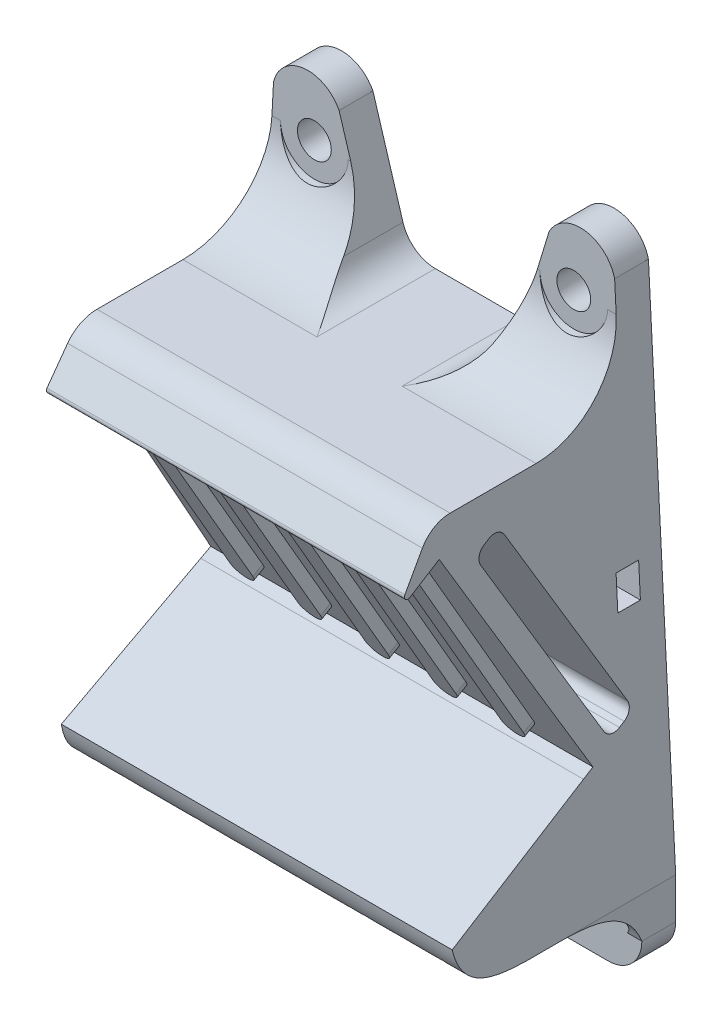
SolidWorks part; units mm, degrees
ref_plane "Alzado" through (0, 0, 0) normal (0, 0, 1) x (1, 0, 0)
ref_plane "Planta" through (0, 0, 0) normal (0, 1, 0) x (1, 0, 0)
ref_plane "Vista lateral" through (0, 0, 0) normal (1, 0, 0) x (0, 0, -1)
sketch "Croquis1" plane through (0, 0, 0) normal (0, 0, 1) x (1, 0, 0)
  line L0 (0, 0) -> (27.8544, 27.8544) construction
  line L1 (0, 0) -> (-42.4264, 42.4264) construction
  line L2 (0, 0) -> (0, 42.4264) construction
  line L3 (15.25, -15.25) -> (-15.25, -15.25) construction
  line L4 (15.25, -15.25) -> (15.25, 15.25) construction
  line L5 (15.25, 15.25) -> (-15.25, 15.25) construction
  line L6 (-15.25, -15.25) -> (-15.25, 15.25) construction
  line L7 (15.25, -15.25) -> (-15.25, 15.25) construction
  line L8 (15.25, 15.25) -> (-15.25, -15.25) construction
  line L9 (0, 42.4264) -> (-20, 42.4264) construction
  line L10 (-42.4264, 42.4264) -> (-38.8909, 45.9619) construction
  line L11 (-38.8909, 45.9619) -> (-31.0962, 38.1673) construction
  line L13 (-42.4264, 42.4264) -> (-45.9619, 38.8909) construction
  line L14 (-45.9619, 38.8909) -> (-38.1673, 31.0962) construction
  line L16 (38.8909, 45.9619) -> (31.0962, 38.1673) construction
  line L17 (42.4264, 42.4264) -> (38.8909, 45.9619) construction
  line L18 (42.4264, 42.4264) -> (45.9619, 38.8909) construction
  line L19 (-45.9619, -38.8909) -> (-38.1673, -31.0962) construction
  line L20 (0, 0) -> (-15.25, 0) construction
  line L21 (45.9619, 38.8909) -> (38.1673, 31.0962) construction
  line L22 (42.4264, -42.4264) -> (45.9619, -38.8909) construction
  line L23 (42.4264, -42.4264) -> (38.8909, -45.9619) construction
  line L24 (38.8909, -45.9619) -> (31.0962, -38.1673) construction
  line L27 (-38.8909, -45.9619) -> (-31.0962, -38.1673) construction
  line L28 (-42.4264, -42.4264) -> (-38.8909, -45.9619) construction
  line L29 (-42.4264, -42.4264) -> (-45.9619, -38.8909) construction
  line L30 (45.9619, -38.8909) -> (38.1673, -31.0962) construction
  line L31 (-15, 80) -> (15, 80) construction
  line L32 (0, -15.25) -> (0, -80) construction
  line L36 (-15, -80) -> (15, -80) construction
  line L41 (-12.268, -54) -> (-12.268, -67.5) construction
  line L43 (-10.268, -54) -> (-10.268, -67.5) construction
  line L105 (0, -80) -> (0, -83) construction
  line L106 (-15, -80) -> (0, -83) construction
  line L127 (15, -80) -> (0, -83) construction
  line L131 (0, 80) -> (0, 83) construction
  line L132 (-15, 80) -> (15, 80) construction
  line L136 (15, 80) -> (0, 83) construction
  line L157 (-15, 80) -> (0, 83) construction
  line L160 (-14, 30) -> (-17.8891, 33.8891) construction
  line L161 (-31.0962, 38.1673) -> (-22.6531, 29.7242) construction
  line L162 (-17.5359, 31.6883) -> (-15, 80) construction
  line L163 (17.5359, 31.6883) -> (15, 80) construction
  line L164 (31.0962, 38.1673) -> (22.6531, 29.7242) construction
  line L165 (31.0962, -38.1673) -> (22.6531, -29.7242) construction
  line L166 (17.5359, -31.6883) -> (15, -80) construction
  line L167 (-17.5359, -31.6883) -> (-15, -80) construction
  line L168 (-31.0962, -38.1673) -> (-22.6531, -29.7242) construction
  line L169 (-8.268, -54) -> (-8.268, -67.5) construction
  line L170 (-6.268, -54) -> (-6.268, -67.5) construction
  line L171 (-4.268, -54) -> (-4.268, -67.5) construction
  line L172 (-2.268, -54) -> (-2.268, -67.5) construction
  line L173 (-8.268, -35) -> (-8.268, -48.5) construction
  line L174 (-6.268, -35) -> (-6.268, -48.5) construction
  line L175 (-4.268, -35) -> (-4.268, -48.5) construction
  line L176 (-2.268, -35) -> (-2.268, -48.5) construction
  line L177 (-12.268, -35) -> (-12.268, -48.5) construction
  line L178 (-10.268, -35) -> (-10.268, -48.5) construction
  line L179 (10.268, -35) -> (10.268, -48.5) construction
  line L180 (12.268, -35) -> (12.268, -48.5) construction
  line L181 (2.268, -35) -> (2.268, -48.5) construction
  line L182 (4.268, -35) -> (4.268, -48.5) construction
  line L183 (6.268, -35) -> (6.268, -48.5) construction
  line L184 (8.268, -35) -> (8.268, -48.5) construction
  line L185 (2.268, -54) -> (2.268, -67.5) construction
  line L186 (4.268, -54) -> (4.268, -67.5) construction
  line L187 (6.268, -54) -> (6.268, -67.5) construction
  line L188 (8.268, -54) -> (8.268, -67.5) construction
  line L189 (10.268, -54) -> (10.268, -67.5) construction
  line L190 (12.268, -54) -> (12.268, -67.5) construction
  line L191 (12.268, 54) -> (12.268, 67.5) construction
  line L192 (10.268, 54) -> (10.268, 67.5) construction
  line L193 (8.268, 54) -> (8.268, 67.5) construction
  line L194 (6.268, 54) -> (6.268, 67.5) construction
  line L195 (4.268, 54) -> (4.268, 67.5) construction
  line L196 (2.268, 54) -> (2.268, 67.5) construction
  line L197 (8.268, 35) -> (8.268, 48.5) construction
  line L198 (6.268, 35) -> (6.268, 48.5) construction
  line L199 (4.268, 35) -> (4.268, 48.5) construction
  line L200 (2.268, 35) -> (2.268, 48.5) construction
  line L201 (12.268, 35) -> (12.268, 48.5) construction
  line L202 (10.268, 35) -> (10.268, 48.5) construction
  line L203 (-10.268, 35) -> (-10.268, 48.5) construction
  line L204 (-12.268, 35) -> (-12.268, 48.5) construction
  line L205 (-2.268, 35) -> (-2.268, 48.5) construction
  line L206 (-4.268, 35) -> (-4.268, 48.5) construction
  line L207 (-6.268, 35) -> (-6.268, 48.5) construction
  line L208 (-8.268, 35) -> (-8.268, 48.5) construction
  line L209 (-2.268, 54) -> (-2.268, 67.5) construction
  line L210 (-4.268, 54) -> (-4.268, 67.5) construction
  line L211 (-6.268, 54) -> (-6.268, 67.5) construction
  line L212 (-8.268, 54) -> (-8.268, 67.5) construction
  line L213 (-10.268, 54) -> (-10.268, 67.5) construction
  line L214 (-12.268, 54) -> (-12.268, 67.5) construction
  line L215 (-0.621, -15.7817) -> (-8.2129, -22.282) construction
  line L216 (-7.5625, -24.0416) -> (8.3607, -24.0416) construction
  line L217 (8.9758, -22.2532) -> (0.6445, -15.7529) construction
  line L218 (-7.5625, 24.0416) -> (8.3607, 24.0416) construction
  line L219 (8.9758, 22.2532) -> (0.6445, 15.7529) construction
  line L220 (-0.621, 15.7817) -> (-8.2129, 22.282) construction
  line L221 (-38.1673, 31.0962) -> (-28.2843, 21.2132) construction
  line L222 (-28.2843, -21.2132) -> (-38.1673, -31.0962) construction
  line L223 (28.2843, -21.2132) -> (38.1673, -31.0962) construction
  line L224 (38.1673, 31.0962) -> (28.2843, 21.2132) construction
  line L225 (-17.5359, 31.6883) -> (-15, 80)
  line L226 (-15, 80) -> (0, 83)
  line L227 (0, 83) -> (15, 80)
  line L228 (15, 80) -> (17.5359, 31.6883)
  line L229 (17.5359, 31.6883) -> (17.5359, -31.6883)
  line L230 (17.5359, -31.6883) -> (15, -80)
  line L231 (15, -80) -> (0, -83)
  line L232 (0, -83) -> (-15, -80)
  line L233 (-15, -80) -> (-17.5359, -31.6883)
  line L234 (-17.5359, -31.6883) -> (-17.5359, 31.6883)
  circle A0 centre (-15.25, 15.25) radius 4 construction
  circle A1 centre (-24.0416, 24.0416) radius 1.5 construction
  circle A2 centre (-38.8909, 38.8909) radius 1.5 construction
  circle A5 centre (38.8909, 38.8909) radius 1.5 construction
  circle A6 centre (24.0416, 24.0416) radius 1.5 construction
  circle A7 centre (15.25, 15.25) radius 4 construction
  circle A8 centre (15.25, -15.25) radius 4 construction
  circle A9 centre (24.0416, -24.0416) radius 1.5 construction
  circle A10 centre (38.8909, -38.8909) radius 1.5 construction
  circle A12 centre (-15.25, -15.25) radius 4 construction
  circle A13 centre (-24.0416, -24.0416) radius 1.5 construction
  circle A14 centre (-38.8909, -38.8909) radius 1.5 construction
  circle A18 centre (0, 0) radius 3.5 construction
  circle A19 centre (-11.5, -75) radius 1.5 construction
  circle A21 centre (-14, 30) radius 1.5 construction
  arc A27 (-12.268, -54) -> (-10.268, -54) centre (-11.268, -54) cw construction
  arc A28 (-12.268, -67.5) -> (-10.268, -67.5) centre (-11.268, -67.5) ccw construction
  circle A111 centre (11.5, -75) radius 1.5 construction
  circle A112 centre (11.5, 75) radius 1.5 construction
  circle A137 centre (-11.5, 75) radius 1.5 construction
  arc A138 (-22.6531, 29.7242) -> (-17.5359, 31.6883) centre (-20.5318, 31.8455) ccw construction
  arc A139 (22.6531, 29.7242) -> (17.5359, 31.6883) centre (20.5318, 31.8455) cw construction
  arc A140 (22.6531, -29.7242) -> (17.5359, -31.6883) centre (20.5318, -31.8455) ccw construction
  arc A141 (-22.6531, -29.7242) -> (-17.5359, -31.6883) centre (-20.5318, -31.8455) cw construction
  circle A142 centre (14, 30) radius 1.5 construction
  circle A143 centre (14, -30) radius 1.5 construction
  circle A144 centre (-14, -30) radius 1.5 construction
  arc A145 (-8.268, -67.5) -> (-6.268, -67.5) centre (-7.268, -67.5) ccw construction
  arc A146 (-8.268, -54) -> (-6.268, -54) centre (-7.268, -54) cw construction
  arc A147 (-4.268, -67.5) -> (-2.268, -67.5) centre (-3.268, -67.5) ccw construction
  arc A148 (-4.268, -54) -> (-2.268, -54) centre (-3.268, -54) cw construction
  arc A149 (-8.268, -48.5) -> (-6.268, -48.5) centre (-7.268, -48.5) ccw construction
  arc A150 (-8.268, -35) -> (-6.268, -35) centre (-7.268, -35) cw construction
  arc A151 (-4.268, -48.5) -> (-2.268, -48.5) centre (-3.268, -48.5) ccw construction
  arc A152 (-4.268, -35) -> (-2.268, -35) centre (-3.268, -35) cw construction
  arc A153 (-12.268, -48.5) -> (-10.268, -48.5) centre (-11.268, -48.5) ccw construction
  arc A154 (-12.268, -35) -> (-10.268, -35) centre (-11.268, -35) cw construction
  arc A155 (12.268, -35) -> (10.268, -35) centre (11.268, -35) ccw construction
  arc A156 (12.268, -48.5) -> (10.268, -48.5) centre (11.268, -48.5) cw construction
  arc A157 (4.268, -35) -> (2.268, -35) centre (3.268, -35) ccw construction
  arc A158 (4.268, -48.5) -> (2.268, -48.5) centre (3.268, -48.5) cw construction
  arc A159 (8.268, -35) -> (6.268, -35) centre (7.268, -35) ccw construction
  arc A160 (8.268, -48.5) -> (6.268, -48.5) centre (7.268, -48.5) cw construction
  arc A161 (4.268, -54) -> (2.268, -54) centre (3.268, -54) ccw construction
  arc A162 (4.268, -67.5) -> (2.268, -67.5) centre (3.268, -67.5) cw construction
  arc A163 (8.268, -54) -> (6.268, -54) centre (7.268, -54) ccw construction
  arc A164 (8.268, -67.5) -> (6.268, -67.5) centre (7.268, -67.5) cw construction
  arc A165 (12.268, -67.5) -> (10.268, -67.5) centre (11.268, -67.5) cw construction
  arc A166 (12.268, -54) -> (10.268, -54) centre (11.268, -54) ccw construction
  arc A167 (12.268, 54) -> (10.268, 54) centre (11.268, 54) cw construction
  arc A168 (12.268, 67.5) -> (10.268, 67.5) centre (11.268, 67.5) ccw construction
  arc A169 (8.268, 67.5) -> (6.268, 67.5) centre (7.268, 67.5) ccw construction
  arc A170 (8.268, 54) -> (6.268, 54) centre (7.268, 54) cw construction
  arc A171 (4.268, 67.5) -> (2.268, 67.5) centre (3.268, 67.5) ccw construction
  arc A172 (4.268, 54) -> (2.268, 54) centre (3.268, 54) cw construction
  arc A173 (8.268, 48.5) -> (6.268, 48.5) centre (7.268, 48.5) ccw construction
  arc A174 (8.268, 35) -> (6.268, 35) centre (7.268, 35) cw construction
  arc A175 (4.268, 48.5) -> (2.268, 48.5) centre (3.268, 48.5) ccw construction
  arc A176 (4.268, 35) -> (2.268, 35) centre (3.268, 35) cw construction
  arc A177 (12.268, 48.5) -> (10.268, 48.5) centre (11.268, 48.5) ccw construction
  arc A178 (12.268, 35) -> (10.268, 35) centre (11.268, 35) cw construction
  arc A179 (-12.268, 35) -> (-10.268, 35) centre (-11.268, 35) ccw construction
  arc A180 (-12.268, 48.5) -> (-10.268, 48.5) centre (-11.268, 48.5) cw construction
  arc A181 (-4.268, 35) -> (-2.268, 35) centre (-3.268, 35) ccw construction
  arc A182 (-4.268, 48.5) -> (-2.268, 48.5) centre (-3.268, 48.5) cw construction
  arc A183 (-8.268, 35) -> (-6.268, 35) centre (-7.268, 35) ccw construction
  arc A184 (-8.268, 48.5) -> (-6.268, 48.5) centre (-7.268, 48.5) cw construction
  arc A185 (-4.268, 54) -> (-2.268, 54) centre (-3.268, 54) ccw construction
  arc A186 (-4.268, 67.5) -> (-2.268, 67.5) centre (-3.268, 67.5) cw construction
  arc A187 (-8.268, 54) -> (-6.268, 54) centre (-7.268, 54) ccw construction
  arc A188 (-8.268, 67.5) -> (-6.268, 67.5) centre (-7.268, 67.5) cw construction
  arc A189 (-12.268, 67.5) -> (-10.268, 67.5) centre (-11.268, 67.5) cw construction
  arc A190 (-12.268, 54) -> (-10.268, 54) centre (-11.268, 54) ccw construction
  arc A191 (8.3607, -24.0416) -> (8.9758, -22.2532) centre (8.3607, -23.0416) ccw construction
  arc A192 (0.6445, -15.7529) -> (-0.621, -15.7817) centre (0.0294, -16.5413) ccw construction
  arc A193 (-8.2129, -22.282) -> (-7.5625, -24.0416) centre (-7.5625, -23.0416) ccw construction
  arc A194 (8.3607, 24.0416) -> (8.9758, 22.2532) centre (8.3607, 23.0416) cw construction
  arc A195 (0.6445, 15.7529) -> (-0.621, 15.7817) centre (0.0294, 16.5413) cw construction
  arc A196 (-8.2129, 22.282) -> (-7.5625, 24.0416) centre (-7.5625, 23.0416) cw construction
  arc A197 (-28.2843, 21.2132) -> (-28.2843, -21.2132) centre (-49.4975, 0) cw construction
  arc A198 (28.2843, 21.2132) -> (28.2843, -21.2132) centre (49.4975, 0) ccw construction
  circle A199 centre (-11.5, 75) radius 1.5
  circle A200 centre (11.5, 75) radius 1.5
  circle A201 centre (14, 30) radius 1.5
  circle A202 centre (-14, 30) radius 1.5
  circle A203 centre (-14, -30) radius 1.5
  circle A204 centre (14, -30) radius 1.5
  circle A205 centre (-11.5, -75) radius 1.5
  circle A206 centre (11.5, -75) radius 1.5
  point P35 (-34.9935, 42.0646)
  point P37 (44.1942, 40.6586)
  point P45 (44.1942, -40.6586)
  point P52 (-16.268, -55.8441)
  point P61 (-34.9935, -42.0646)
  point P70 (0, 80)
  point P260 (-7.0711, 0)
  dimension "D2" = 8
  dimension "D4" = 5
  dimension "D8" = 14.75
  dimension "D10" = 3
  dimension "D11" = 3
  dimension "D13" = 11.5
  dimension "D15" = 3
  dimension "D16" = 14
  dimension "D18" = 3
  dimension "D24" = 3
  dimension "D26" = 1
  dimension "D27" = 7
  dimension "D28" = 30
  dimension "D1" = 30.5
  dimension "D3" = 60
  dimension "D5" = 21
  dimension "D6" = 15
  dimension "D7" = 5
  dimension "D9" = 5
  dimension "D12" = 80
  dimension "D14" = 5
  dimension "D17" = 4
  dimension "D19" = 2
  dimension "D20" = 13.5
  dimension "D21" = 7.5
  dimension "D22" = 3
  dimension "D25" = 2
  dimension "D23" = 5.5
extrude "Saliente-Extruir1" add sketch "Croquis1" along normal blind 2
sketch "Croquis2" plane through (0, 0, 2) normal (0, 0, 1) x (1, 0, 0)
  line L1 (0, 83) -> (-15, 80) construction
  line L2 (-7.5, 81.5) -> (7.5, 81.5) construction
  line L3 (15, 80) -> (0, 83) construction
  line L4 (7.5, 81.5) -> (15, 80) construction
  line L5 (0, 81.5) -> (0, 67.5) construction
  line L6 (-10, 75) -> (-8.2794, 75) construction
  line L7 (-10.0971, 80.9806) -> (-8.2794, 75) construction
  line L8 (-10.0971, 80.9806) -> (-6, 67.5)
  line L9 (-6, 67.5) -> (6, 67.5)
  line L10 (-10.0971, 80.9806) -> (0, 83)
  line L11 (10.0971, 80.9806) -> (6, 67.5)
  line L12 (10.0971, 80.9806) -> (0, 83)
  line L13 (-10, 75) -> (-10, 65) construction
  line L14 (-10, 65) -> (-11.3105, 40.0344)
  line L15 (0, 67.5) -> (0, 30) construction
  line L16 (-10.6552, 52.5172) -> (0, 51.9579) construction
  line L17 (0, 51.9579) -> (-2, 52.0629) construction
  line L18 (0, 30) -> (0, 37.5) construction
  line L19 (-11.3105, 40.0344) -> (-2, 52.0629)
  line L20 (-2, 52.0629) -> (-10, 65)
  line L21 (2, 52.0629) -> (10, 65)
  line L22 (10, 65) -> (11.3105, 40.0344)
  line L23 (11.3105, 40.0344) -> (2, 52.0629)
  line L24 (-12.5, 30) -> (12.5, 30) construction
  line L25 (0, 37.5) -> (-7.5, 37.5) construction
  line L26 (0, 30) -> (-7.5, 37.5)
  line L27 (-7.5, 37.5) -> (0, 47.1895)
  line L28 (0, 30) -> (7.5, 37.5)
  line L29 (7.5, 37.5) -> (0, 47.1895)
  line L30 (-17.5359, 0) -> (17.5359, 0) construction
  line L31 (-17.5359, 31.6883) -> (-17.5359, -31.6883) construction
  line L32 (17.5359, -31.6883) -> (17.5359, 31.6883) construction
  line L33 (-10.5359, 18) -> (10.5359, 18)
  line L34 (-12.5, 25) -> (12.5, 25)
  line L35 (-12.5, 25) -> (-12.5, 22)
  line L36 (-12.5, 22) -> (12.5, 22)
  line L37 (12.5, 25) -> (12.5, 22)
  line L38 (-10.5359, -1.5) -> (-10.5359, 1.5)
  line L39 (-10.5359, 1.5) -> (10.5359, 1.5)
  line L40 (10.5359, 1.5) -> (10.5359, -1.5)
  line L41 (0, 1.5) -> (0, 4.5) construction
  line L42 (-10.5359, 18) -> (0, 4.5)
  line L43 (0, 4.5) -> (10.5359, 18)
  line L44 (0, -1.5) -> (0, -4.5) construction
  line L45 (0, -37.5) -> (-7.5, -37.5) construction
  line L46 (-12.5, -30) -> (12.5, -30) construction
  line L47 (0, -30) -> (0, -37.5) construction
  line L48 (0, -51.9579) -> (-2, -52.0629) construction
  line L49 (-10.6552, -52.5172) -> (0, -51.9579) construction
  line L50 (0, -67.5) -> (0, -30) construction
  line L51 (-10, -75) -> (-10, -65) construction
  line L52 (-10.0971, -80.9806) -> (-8.2794, -75) construction
  line L53 (-10, -75) -> (-8.2794, -75) construction
  line L54 (0, -81.5) -> (0, -67.5) construction
  line L55 (7.5, -81.5) -> (15, -80) construction
  line L56 (-7.5, -81.5) -> (7.5, -81.5) construction
  line L57 (-15, -80) -> (-7.5, -81.5) construction
  line L58 (0, -4.5) -> (10.5359, -18)
  line L59 (-10.5359, -18) -> (0, -4.5)
  line L60 (-10.5359, -1.5) -> (10.5359, -1.5)
  line L61 (12.5, -25) -> (12.5, -22)
  line L62 (-12.5, -22) -> (12.5, -22)
  line L63 (-12.5, -25) -> (-12.5, -22)
  line L64 (-12.5, -25) -> (12.5, -25)
  line L65 (-10.5359, -18) -> (10.5359, -18)
  line L66 (7.5, -37.5) -> (0, -47.1895)
  line L67 (0, -30) -> (7.5, -37.5)
  line L68 (-7.5, -37.5) -> (0, -47.1895)
  line L69 (0, -30) -> (-7.5, -37.5)
  line L70 (11.3105, -40.0344) -> (2, -52.0629)
  line L71 (10, -65) -> (11.3105, -40.0344)
  line L72 (2, -52.0629) -> (10, -65)
  line L73 (-2, -52.0629) -> (-10, -65)
  line L74 (-11.3105, -40.0344) -> (-2, -52.0629)
  line L75 (-10, -65) -> (-11.3105, -40.0344)
  line L76 (10.0971, -80.9806) -> (0, -83)
  line L77 (10.0971, -80.9806) -> (6, -67.5)
  line L78 (-10.0971, -80.9806) -> (0, -83)
  line L79 (-6, -67.5) -> (6, -67.5)
  line L80 (-10.0971, -80.9806) -> (-6, -67.5)
  circle A0 centre (-11.5, 75) radius 1.5 construction
  circle A1 centre (-14, 30) radius 1.5 construction
  circle A2 centre (14, 30) radius 1.5 construction
  point P85 (10.5359, 0)
  point P86 (-10.5359, 0)
  dimension "D1" = 14
  dimension "D2" = 10
  dimension "D3" = 25
  dimension "D4" = 2
  dimension "D5" = 7.5
  dimension "D6" = 5
  dimension "D7" = 3
  dimension "D8" = 4
  dimension "D9" = 1.5
  dimension "D10" = 7
  dimension "D11" = 7
  dimension "D12" = 3
  dimension "D13" = 6
  dimension "D14" = 5
extrude "Cortar-Extruir1" cut sketch "Croquis2" against normal up to vertex (2 mm away) up to point (-17.5359, -31.6883, 0)
fillet "Redondeo2" radius 1 38 edges at (0, -30, 1) (11.3105, -40.0344, 1) (10, -65, 1) (2, -52.0629, 1) (-10, -65, 1) (-7.5, -37.5, 1) (7.5, -37.5, 1) (-2, -52.0629, 1) (-11.3105, -40.0344, 1) (12.5, 22, 1) (-12.5, 22, 1) (-12.5, 25, 1) (12.5, 25, 1) (10.5359, 18, 1) (-10.5359, 18, 1) (0, 4.5, 1) (10.5359, -1.5, 1) (-10.5359, -1.5, 1) (10.5359, 1.5, 1) (-10.5359, 1.5, 1) (10.5359, -18, 1) (0, -4.5, 1) (-10.5359, -18, 1) (12.5, -25, 1) (-12.5, -25, 1) (12.5, -22, 1) (-12.5, -22, 1) (0, 30, 1) (7.5, 37.5, 1) (-7.5, 37.5, 1) (0, 47.1895, 1) (11.3105, 40.0344, 1) (10, 65, 1) (2, 52.0629, 1) (-2, 52.0629, 1) (-11.3105, 40.0344, 1) (-10, 65, 1) (0, -47.1895, 1)
fillet "Redondeo1" radius 3 16 edges at (15, -80, 1) (-15, -80, 1) (15, 80, 1) (-15, 80, 1) (-6, -67.5, 1) (6, -67.5, 1) (10.0971, -80.9806, 1) (-10.0971, -80.9806, 1) (10.0971, 80.9806, 1) (6, 67.5, 1) (-6, 67.5, 1) (-10.0971, 80.9806, 1) (17.5359, -31.6883, 1) (17.5359, 31.6883, 1) (-17.5359, -31.6883, 1) (-17.5359, 31.6883, 1)
sketch "Croquis3" plane through (0, 0, 2) normal (0, 0, 1) x (1, 0, 0)
  line L0 (-17.5359, 31.6096) -> (-15.1222, 77.6726)
  line L1 (-9.306, 78.3777) -> (-6.6466, 69.6276)
  line L2 (3.7763, 67.5) -> (-3.7763, 67.5)
  line L3 (-3.7763, 67.5) -> (3.7763, 67.5) construction
  line L4 (14.5359, 25) -> (-14.5359, 25)
  line L5 (11.5, 25) -> (-11.5, 25) construction
  line L6 (-17.5359, 31.6096) -> (-17.5359, -31.6096) construction
  line L7 (-17.5359, 28) -> (-17.5359, 31.6096)
  line L8 (0, 67.5) -> (0, 25) construction
  line L9 (17.5359, 28) -> (17.5359, 31.6096)
  line L10 (9.306, 78.3777) -> (6.6466, 69.6276)
  line L11 (17.5359, 31.6096) -> (15.1222, 77.6726)
  arc A0 (-15.1222, 77.6726) -> (-9.306, 78.3777) centre (-12.0835, 76.9476) cw
  arc A1 (-6.6466, 69.6276) -> (-3.7763, 67.5) centre (-3.7763, 70.5) ccw
  circle A2 centre (-11.5, 75) radius 1.5
  circle A3 centre (-14, 30) radius 1.5
  circle A4 centre (14, 30) radius 1.5
  circle A5 centre (11.5, 75) radius 1.5
  arc A6 (6.6466, 69.6276) -> (3.7763, 67.5) centre (3.7763, 70.5) cw
  arc A7 (15.1222, 77.6726) -> (9.306, 78.3777) centre (12.0835, 76.9476) ccw
  arc A8 (17.5359, 28) -> (14.5359, 25) centre (14.5359, 28) cw
  arc A9 (-14.5359, 25) -> (-17.5359, 28) centre (-14.5359, 28) cw
  point P41 (17.5359, 25)
  point P44 (-17.5359, 25)
  dimension "D1" = 3
extrude "Saliente-Extruir2" add sketch "Croquis3" along normal blind 3
sketch "Croquis4" plane through (0, 0, 2) normal (0, 0, 1) x (1, 0, 0)
  line L1 (-41.3462, 95.3241) -> (47.8508, 95.3241)
  line L2 (-41.3462, 95.3241) -> (-41.3462, -93.5853)
  line L3 (-41.3462, -93.5853) -> (47.8508, -93.5853)
  line L4 (47.8508, 95.3241) -> (47.8508, -93.5853)
extrude "Cortar-Extruir2" cut sketch "Croquis4" against normal up to vertex (2 mm away) up to point (-17.5318, -31.7668, 0)
sketch "Croquis5" plane through (0, 0, 5) normal (0, 0, 1) x (1, 0, 0)
  line L0 (0, 67.5) -> (-15.6552, 67.5)
  line L1 (3.7763, 67.5) -> (-3.7763, 67.5) construction
  line L2 (-15.1222, 77.6726) -> (-17.5359, 31.6096) construction
  line L3 (-15.6552, 67.5) -> (-17.3297, 35.5452)
  line L5 (17.5359, 31.6096) -> (15.1222, 77.6726) construction
  line L7 (15.6552, 67.5) -> (0, 67.5)
  line L8 (-17.3297, 35.5452) -> (17.3297, 35.5452)
  line L9 (17.3297, 35.5452) -> (15.6552, 67.5)
extrude "Saliente-Extruir3" add sketch "Croquis5" along normal blind 20
fillet "Redondeo3" radius 7.5 1 edges at (9.7158, 67.5, 5) type face fillet first side face at (0, 67.5, 9.25) second side face at (10, 75, 5)
fillet "Redondeo4" radius 7.5 1 edges at (-9.7158, 67.5, 5) type face fillet first side face at (0, 67.5, 11.125) second side face at (-10, 75, 5)
sketch "Croquis6" plane through (-19.1397, 1.0029, 0) normal (-0.9986, 0.0523, 0) x (0, 0, 1)
  line L0 (16, 63.5883) -> (5, 44.5357)
  line L1 (25, 66.5883) -> (12.5, 66.5883) construction
  line L2 (2, 76.7748) -> (2, 30.6486) construction
  line L3 (16, 63.5883) -> (18.1651, 62.3383)
  line L4 (18.1651, 62.3383) -> (7.1651, 43.2857)
  line L5 (7.1651, 43.2857) -> (5, 44.5357)
  line L6 (22.1085, 63.1685) -> (5.6085, 34.5897) construction
  line L7 (25, 34.5897) -> (5, 34.5897) construction
  line L8 (22.1085, 63.1685) -> (25, 61.4991)
  line L9 (25, 66.5883) -> (25, 34.5897) construction
  line L10 (25, 61.4991) -> (21.7651, 66.5883)
  line L13 (22.1085, 63.1685) -> (9.6085, 41.5179)
  line L14 (9.6085, 41.5179) -> (25, 32.6316)
  line L15 (25, 61.4991) -> (25, 32.6316)
  line L16 (21.7651, 66.5883) -> (25, 66.5883)
  line L17 (25, 66.5883) -> (25, 61.4991)
  line L18 (2, 53.7117) -> (4, 53.7117) construction
  line L19 (4, 53.7117) -> (4, 52.2117)
  line L20 (4, 52.2117) -> (6, 52.2117)
  line L21 (6, 52.2117) -> (6, 55.2117)
  line L22 (6, 55.2117) -> (4, 55.2117)
  line L23 (4, 55.2117) -> (4, 53.7117)
  line M17 (25, 34.5897) -> (25, 66.5883)
  line M18 (25, 66.5883) -> (12.5, 66.5883)
  dimension "D1" = 3
  dimension "D2" = 22
  dimension "D3" = 30
  dimension "D4" = 3
  dimension "D5" = 2.5
  dimension "D6" = 3
  dimension "D7" = 25
  dimension "D8" = 2
  dimension "D9" = 1.5
  dimension "D10" = 2
  dimension "D11" = 1.5
  dimension "D12" = 8
extrude "Cortar-Extruir3" cut sketch "Croquis6" along direction (1, 0, 0) on the side against the normal up to surface (31.6684 mm away) contours L13 L14 L8 M17 | L5 L4 L3 L0 | L10 M17 M18 | L22 L23 L19 L20 L21 region at (-16.3434, 54.3667, 11.5825) region at (-15.744, 65.8059, 23.9217) region at (-16.6894, 47.7648, 19.7171) region at (-16.329, 54.6411, 5) up to face at (16.2922, 55.3446, 9.4385)
sketch "Croquis9" plane through (-19.1397, 1.0029, 0) normal (-0.9986, 0.0523, 0) x (0, 0, 1)
  line L0 (5, 30.6486) -> (5, 27.0486)
  line L1 (21.6085, 34.5897) -> (5, 34.5897)
  line L2 (5, 34.5897) -> (5, 27.0486)
  line L3 (9.6085, 41.5179) -> (21.6085, 34.5897) construction
  spline S0 degree 3 poles (21.6085, 34.5897) (20.041, 26.6929) (7.9143, 34.4935) (5, 27.0486) knots 0 0 0 0 1 1 1 1
  point P5 (25, 34.5897)
  point P8 (0, 0)
  point P11 (0, 0)
  point P12 (0, 0)
  point P13 (21.6085, 34.5897)
  point P16 (19.938, 31.7322)
  line M17 (5, 30.6486) -> (5, 34.5897)
  line M18 (5, 34.5897) -> (21.6085, 34.5897)
extrude "Saliente-Extruir4" add sketch "Croquis9" along direction (1, 0, 0) on the side against the normal up to surface (35.4486 mm away) contours S0 L0 M18 M17 region at (-17.4417, 33.4077, 12.2) up to face at (16.329, 54.6411, 5)
sketch "Croquis10" plane through (0, 0, 2) normal (0, 0, -1) x (-1, 0, 0)
  circle A0 centre (11.5, 75) radius 3
  circle A1 centre (-11.5, 75) radius 3
  circle A2 centre (14, 30) radius 3
  circle A3 centre (-14, 30) radius 3
  dimension "D1" = 6
  dimension "D2" = 6
  dimension "D3" = 6
  dimension "D4" = 6
extrude "Cortar-Extruir4" cut sketch "Croquis10" against normal blind 20 from surface starting at face at (-11.8692, 76.5957, 5)
fillet "Redondeo7" radius 1 4 edges at (0, 44.2294, 7.1651) (0, 45.4777, 5) (0, 64.5041, 16) (0, 63.2558, 18.1651)
fillet "Redondeo8" radius 0.3 1 edges at (0, 62.4178, 25)
fillet "Redondeo9" radius 3 1 edges at (0, 67.5, 21.7651)
sketch "Croquis11" plane through (0, 0, 2) normal (0, 0, -1) x (-1, 0, 0)
  line L0 (17.5359, 31.6096) -> (23.9295, 31.9446)
  line L1 (23.9295, 31.9446) -> (24.542, 20.2547)
  line L2 (24.542, 20.2547) -> (-26.2275, 20.2547)
  line L4 (-17.5359, 31.6096) -> (-26.2275, 32.065)
  line L5 (-26.2275, 32.065) -> (-26.2275, 20.2547)
  line L6 (17.5359, 31.6096) -> (17.5359, 28)
  line L7 (14.5359, 25) -> (-14.5359, 25)
  line L8 (-17.5359, 28) -> (-17.5359, 31.6096)
  arc A0 (17.5359, 28) -> (14.5359, 25) centre (14.5359, 28) cw
  arc A1 (-14.5359, 25) -> (-17.5359, 28) centre (-14.5359, 28) cw
extrude "Cortar-Extruir5" cut sketch "Croquis11" against normal up to vertex (19.6085 mm away) up to point (17.3297, 35.5452, 21.6085)
sketch "Croquis12" plane through (0, 6.4744, -11.1986) normal (0, -0.5005, 0.8657) x (1, 0, 0)
  line L0 (-15.8342, 66.5457) -> (15.8342, 66.5457)
  line L1 (15.8342, 66.5457) -> (16.9671, 41.5714)
  line L2 (16.9671, 41.5714) -> (-16.9671, 41.5714)
  line L3 (-16.9671, 41.5714) -> (-15.8342, 66.5457)
  line L4 (-7.0842, 64.0739) -> (-7.0842, 44.0739)
  line L6 (-13.0842, 64.0739) -> (-13.0842, 44.0739)
  line L8 (-11.0842, 64.0739) -> (-11.0842, 44.0739)
  line L9 (-5.0842, 64.0739) -> (-5.0842, 44.0739)
  line L10 (-1.0842, 64.0739) -> (-1.0842, 44.0739)
  line L11 (0.9158, 64.0739) -> (0.9158, 44.0739)
  line L12 (4.9158, 64.0739) -> (4.9158, 44.0739)
  line L13 (6.9158, 64.0739) -> (6.9158, 44.0739)
  line L14 (10.9158, 64.0739) -> (10.9158, 44.0739)
  line L15 (12.9158, 64.0739) -> (12.9158, 44.0739)
  arc A0 (-13.0842, 64.0739) -> (-11.0842, 64.0739) centre (-12.0842, 64.0739) cw
  arc A1 (-13.0842, 44.0739) -> (-11.0842, 44.0739) centre (-12.0842, 44.0739) ccw
  arc A2 (-7.0842, 44.0739) -> (-5.0842, 44.0739) centre (-6.0842, 44.0739) ccw
  arc A3 (-7.0842, 64.0739) -> (-5.0842, 64.0739) centre (-6.0842, 64.0739) cw
  arc A4 (-1.0842, 44.0739) -> (0.9158, 44.0739) centre (-0.0842, 44.0739) ccw
  arc A5 (-1.0842, 64.0739) -> (0.9158, 64.0739) centre (-0.0842, 64.0739) cw
  arc A6 (4.9158, 44.0739) -> (6.9158, 44.0739) centre (5.9158, 44.0739) ccw
  arc A7 (4.9158, 64.0739) -> (6.9158, 64.0739) centre (5.9158, 64.0739) cw
  arc A8 (10.9158, 44.0739) -> (12.9158, 44.0739) centre (11.9158, 44.0739) ccw
  arc A9 (10.9158, 64.0739) -> (12.9158, 64.0739) centre (11.9158, 64.0739) cw
  dimension "D1" = 2
  dimension "D2" = 20
  dimension "D3" = 5
  dimension "D4" = 2.75
extrude "Cortar-Extruir6" cut sketch "Croquis12" against normal blind 1
sketch "Croquis13" plane through (-19.1397, 1.0029, 0) normal (-0.9986, 0.0523, 0) x (0, 0, 1)
  line L0 (5.631, 40.2062) -> (5.631, 32.8495) construction
  text T0 "30º"
  point P1 (4.8698, 36.6426)
  point P2 (5.7057, 38.9423)
  point P5 (5.631, 40.2062)
extrude "Cortar-Extruir7" cut sketch "Croquis13" against normal blind 1
